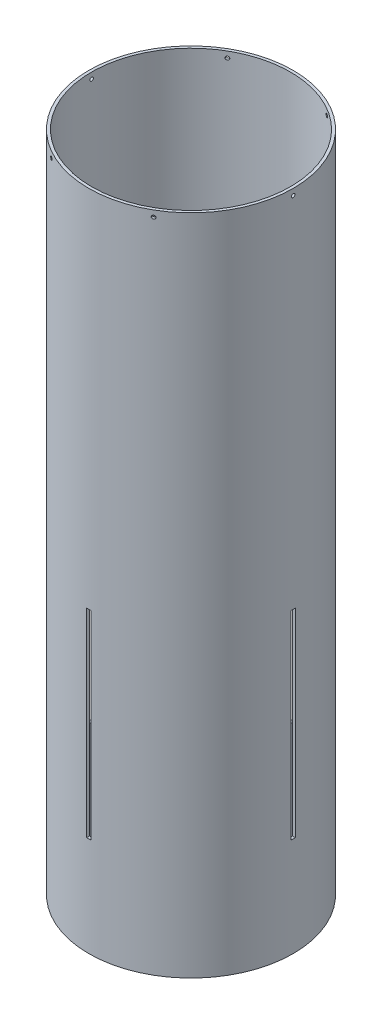
SolidWorks part; units mm, degrees
ref_plane "Front Plane" through (0, 0, 0) normal (0, 0, 1) x (1, 0, 0)
ref_plane "Top Plane" through (0, 0, 0) normal (0, 1, 0) x (1, 0, 0)
ref_plane "Right Plane" through (0, 0, 0) normal (1, 0, 0) x (0, 0, -1)
sketch "Sketch1" plane through (0, 0, 0) normal (0, 1, 0) x (1, 0, 0)
  circle A0 centre (0, 0) radius 76.2
  circle A1 centre (0, 0) radius 78.359
  dimension "D1" = 152.4
  dimension "D2" = 156.718
extrude "Boss-Extrude1" add sketch "Sketch1" along normal blind 508
ref_plane "Plane1" through (0, 0, 0) normal (0.7071, 0, 0.7071) x (0.7071, 0, -0.7071)
ref_axis "Axis1" through (0, 508, 0) along (0, -1, 0)
sketch "Sketch2" plane through (0, 0, 0) normal (1, 0, 0) x (0, 0, -1)
  line L0 (0, 0) -> (0, 76.2)
  line L1 (1.5875, 76.2) -> (-1.5875, 76.2)
  line L2 (1.5875, 76.2) -> (1.5875, 228.6)
  line L3 (1.5875, 228.6) -> (-1.5875, 228.6)
  line L4 (-1.5875, 76.2) -> (-1.5875, 228.6)
  line L5 (1.5875, 76.2) -> (-1.5875, 228.6) construction
  line L6 (1.5875, 228.6) -> (-1.5875, 76.2) construction
  line L7 (78.359, 508) -> (-78.359, 508) construction
  line L8 (78.359, 508) -> (-78.359, 508)
  line L9 (0, 508) -> (0, 503.2375)
  circle A0 centre (0, 503.2375) radius 1.3525
  point P0 (0, 152.4)
  dimension "D4" = 2.7051
  dimension "D1" = 3.175
  dimension "D2" = 152.4
  dimension "D3" = 76.2
  dimension "D5" = 4.7625
extrude "Cut-Extrude1" cut sketch "Sketch2" against normal through all contours L4 L1 L2 L3 region at (0, 152.4, 0)
pattern_circular "CirPattern1" count 4 over 360 about axis through (0, 0, 0) along (0, 1, 0) of "Cut-Extrude1" reverse direction yes
extrude "Cut-Extrude2" cut sketch "Sketch2<3>" against normal through all contours A0 region at (0, 502.3082, 0.9293)
sketch "Sketch2<3>" plane through (0, 0, 0) normal (1, 0, 0) x (0, 0, -1) same geometry as "Sketch2"
pattern_circular "CirPattern2" count 6 over 360 about axis through (0, 508, 0) along (0, -1, 0) of "Cut-Extrude2"
sketch "Sketch3" plane through (0, 0, 0) normal (0.7071, 0, 0.7071) x (0.7071, 0, -0.7071)
  line L0 (0, 0) -> (0, 127) construction
  circle A0 centre (0, 127) radius 3.175
  dimension "D1" = 6.35
  dimension "D2" = 127
extrude "Cut-Extrude3" cut sketch "Sketch3" against normal through all
equation "\"Aft_Lower_Length\"= 20in"
equation "\"D1@Boss-Extrude1\"=\"Aft_Lower_Length\""
equation "\"AB_Coupler_OD_Length\"= 1in"
equation "\"AB_Coupling_Section_Length\"= 0.375in"
equation "\"AB_Coupler_Length\"= \"AB_Coupler_OD_Length\" + \"AB_Coupling_Section_Length\" * 2"
equation "\"AB_Coupler_Num_Screws\"= 6"
equation "\"AB_Coupling_Screw_Diameter\"= 0.1065in"
equation "\"Aft_Upper_Length\"= \"Aft_Section_Length\" - \"Aft_Lower_Length\" - \"AB_Coupler_OD_Length\""
equation "\"Aft_Section_Length\"= 40in"
equation "\"D4@Sketch2\"=\"AB_Coupling_Screw_Diameter\""
equation "\"D5@Sketch2\"=\"AB_Coupling_Section_Length\"/2"
equation "\"D1@CirPattern2\"=\"AB_Coupler_Num_Screws\""
equation "\"Rail_Nut_From_Bottom\"= 5in"
equation "\"Rail_Nut_Diam\"= 0.25in"
equation "\"D1@Sketch3\"=\"Rail_Nut_Diam\""
equation "\"D2@Sketch3\"=\"Rail_Nut_From_Bottom\""
